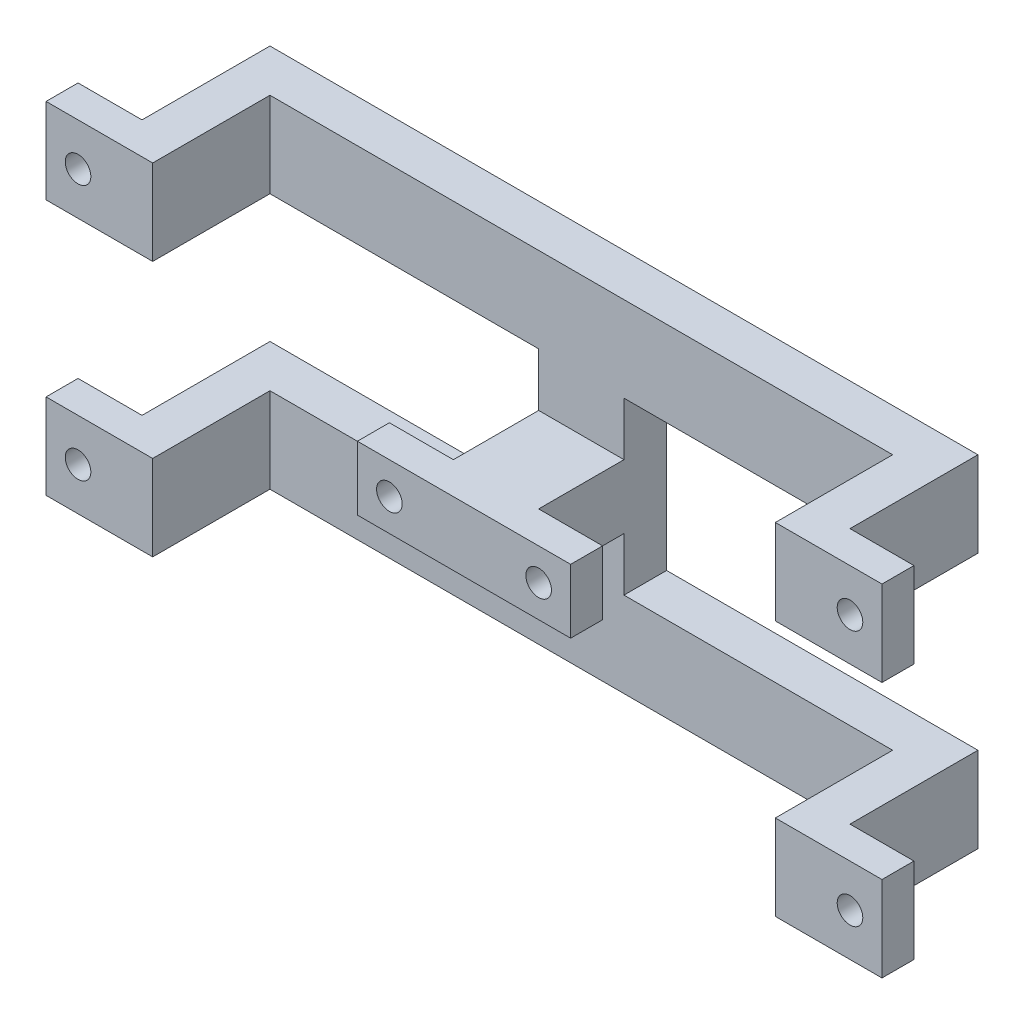
SolidWorks part; units mm, degrees
ref_plane "前视基准面" through (0, 0, 0) normal (0, 0, 1) x (1, 0, 0)
ref_plane "上视基准面" through (0, 0, 0) normal (0, 1, 0) x (1, 0, 0)
ref_plane "右视基准面" through (0, 0, 0) normal (1, 0, 0) x (0, 0, -1)
other "Configuration Table"
sketch "草图1" plane through (0, 0, 0) normal (0, 0, 1) x (1, 0, 0)
  line L0 (-2, 0) -> (2, 0)
  line L1 (-14.6, 8) -> (14.6, 8)
  line L2 (-14.6, 8) -> (-14.6, 4)
  line L3 (-14.6, 4) -> (14.6, 4)
  line L4 (14.6, 8) -> (14.6, 4)
  line L5 (-14.6, -4) -> (14.6, -4)
  line L6 (-14.6, -4) -> (-14.6, -8)
  line L7 (-14.6, -8) -> (14.6, -8)
  line L8 (14.6, -4) -> (14.6, -8)
  line L10 (-2, 4) -> (2, 4)
  line L11 (-2, 4) -> (-2, -4)
  line L12 (-2, -4) -> (2, -4)
  line L13 (2, 4) -> (2, -4)
  line L14 (-14.6, 8) -> (-16.6, 8)
  line L15 (-14.6, 8) -> (-14.6, 4)
  line L16 (-14.6, 4) -> (-16.6, 4)
  line L17 (-16.6, 8) -> (-16.6, 4)
  line L18 (-14.6, -4) -> (-16.6, -4)
  line L19 (-14.6, -4) -> (-14.6, -8)
  line L20 (-14.6, -8) -> (-16.6, -8)
  line L21 (-16.6, -4) -> (-16.6, -8)
  line L22 (14.6, 8) -> (16.6, 8)
  line L23 (14.6, 8) -> (14.6, 4)
  line L24 (14.6, 4) -> (16.6, 4)
  line L25 (16.6, 8) -> (16.6, 4)
  line L26 (14.6, -8) -> (16.6, -8)
  line L27 (14.6, -8) -> (14.6, -4)
  line L28 (14.6, -4) -> (16.6, -4)
  line L29 (16.6, -8) -> (16.6, -4)
  line L30 (-16.6, 8) -> (-19.6, 8)
  line L31 (-16.6, 8) -> (-16.6, 4)
  line L32 (-16.6, 4) -> (-19.6, 4)
  line L33 (-19.6, 8) -> (-19.6, 4)
  line L34 (-16.6, -4) -> (-19.6, -4)
  line L35 (-16.6, -4) -> (-16.6, -8)
  line L36 (-16.6, -8) -> (-19.6, -8)
  line L37 (-19.6, -4) -> (-19.6, -8)
  line L38 (16.6, -8) -> (19.6, -8)
  line L39 (16.6, -8) -> (16.6, -4)
  line L40 (16.6, -4) -> (19.6, -4)
  line L41 (19.6, -8) -> (19.6, -4)
  line L42 (16.6, 4) -> (19.6, 4)
  line L43 (16.6, 4) -> (16.6, 8)
  line L44 (16.6, 8) -> (19.6, 8)
  line L45 (19.6, 4) -> (19.6, 8)
  line L46 (-5, 1.5) -> (5, 1.5)
  line L47 (-5, 1.5) -> (-5, -1.5)
  line L48 (-5, -1.5) -> (5, -1.5)
  line L49 (5, 1.5) -> (5, -1.5)
  circle A3 centre (-3.5, 0) radius 0.6
  circle A4 centre (3.5, 0) radius 0.6
  circle A6 centre (18.1, 6) radius 0.6
  circle A7 centre (18.1, -6) radius 0.6
  circle A8 centre (-18.1, -6) radius 0.6
  circle A9 centre (-18.1, 6) radius 0.6
  point P7 (0, 0)
  point P10 (-2, 0)
  point P11 (0, -4)
  point P18 (0, 8)
  point P43 (0, -1.5)
  point P44 (5, 0)
  point P48 (19.6, -6)
  point P49 (18.1, -8)
  point P50 (-18.1, 4)
  point P51 (-19.6, 6)
  dimension "D4" = 4
  dimension "D1" = 4
  dimension "D2" = 8
  dimension "D7" = 1.2
  dimension "D3" = 29.2
  dimension "D5" = 2
  dimension "D6" = 3
  dimension "D8" = 3
  dimension "D9" = 3
  dimension "D10" = 1.5
  dimension "D11" = 1.5
extrude "凸台-拉伸1" add sketch "草图1" along normal blind 2 contours L5 L8 L7 L6 | L3 L4 L1 L2 | L11 L12 L13 L10
extrude "凸台-拉伸2" add sketch "草图1<6>" along normal blind 7.5 contours L26 L29 L28 L8 | L25 L22 L4 L24 | L14 L17 L16 L2 | L18 L21 L20 L6 | L46 L11 L0 L13 | L11 L48 L13 L0 region at (0, 0.75, 0) region at (0, -0.75, 0) region at (-15.6, 6, 0) region at (-15.6, -6, 0) region at (15.6, 6, 0) region at (15.6, -6, 0)
sketch "草图1<6>" plane through (0, 0, 0) normal (0, 0, 1) x (1, 0, 0) same geometry as "草图1"
extrude "凸台-拉伸3" add sketch "草图1<7>" against normal blind 1.5 from surface contours L42 L45 L44 L25 A6 | L38 L41 L40 L29 A7 | L30 L33 L32 L17 A9 | L34 L37 L36 L21 A8 | L47 L48 L11 L46 A3 | L49 L46 L13 L48 A4 region at (-2.0424, -0.75, 0) region at (2.0424, 0.75, 0) region at (-18.1, 4.05, 0) region at (-16.65, -6, 0) region at (16.65, 6, 0) region at (18.1, -4.05, 0) starting at face at (15.6, 6, 7.5)
sketch "草图1<7>" plane through (0, 0, 0) normal (0, 0, 1) x (1, 0, 0) same geometry as "草图1"
